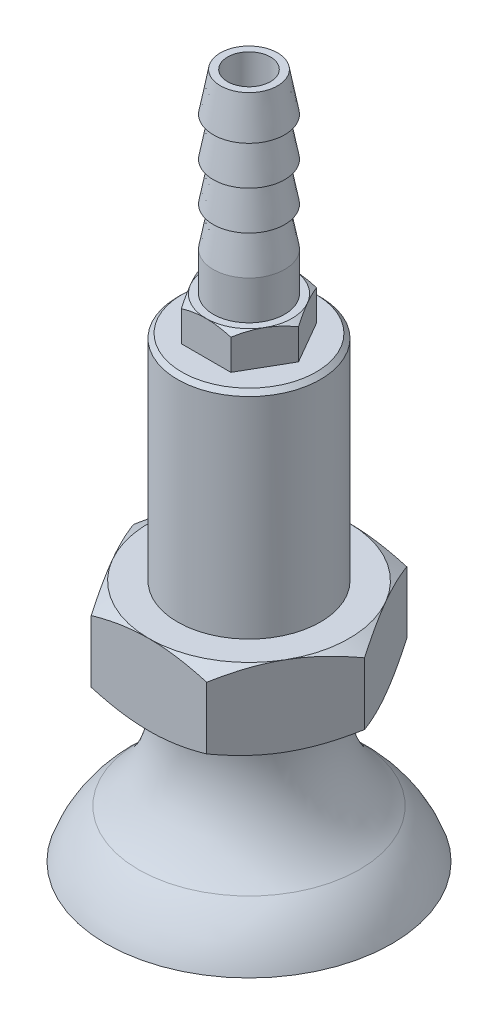
SolidWorks part; units mm, degrees
ref_plane "前视基准面" through (0, 0, 0) normal (0, 0, 1) x (1, 0, 0)
ref_plane "上视基准面" through (0, 0, 0) normal (0, 1, 0) x (1, 0, 0)
ref_plane "右视基准面" through (0, 0, 0) normal (1, 0, 0) x (0, 0, -1)
sketch "草图1" plane through (0, 0, 0) normal (0, 0, 1) x (1, 0, 0)
  line L0 (0, 24) -> (0, -24) construction
  line L1 (0, 24) -> (-2.5, 24)
  line L2 (-2.5, 24) -> (-2.5, 10.4)
  line L3 (-2.5, 10.4) -> (-3, 10.4)
  line L4 (-3, 10.4) -> (-3, 8)
  line L5 (-3, 8) -> (-5, 8)
  line L6 (-5, 8) -> (-5, 5.8)
  line L8 (-7, 5.8) -> (-7, -2.6)
  line L10 (-5, -2.6) -> (-5, -4.8)
  line L12 (-7, -7) -> (-7, -12.6)
  line L14 (-5, -12.6) -> (-5, -14)
  line L16 (-6, -19.5) -> (-10, -24)
  line L22 (0, -24) -> (-29.6075, -24) construction
  line L23 (-5, -4.8) -> (-5, -7)
  line L24 (-5, -14) -> (-6, -19.5)
  line L25 (-3.35, -20.4274) -> (-2.15, -20.4274)
  line L26 (-2.15, -20.4274) -> (-2.15, -9.8)
  line L27 (-2.15, -9.8) -> (0, -9.8)
  line L28 (-3.35, -20.4274) -> (-3.35, -21.7)
  arc A0 (-10, -24) -> (-6, -19.5) centre (-2.5797, -26.568) cw
  arc A1 (-6, -19.5) -> (-5, -14) centre (-15.9986, -14.8412) ccw
  arc A2 (-10, -24) -> (0, -21.4274) centre (0, -42.1495) cw
  point P3 (0, 0)
  point P21 (-7, 1.6)
  point P27 (-7, -9.8)
  point P31 (-2.5, -20.4274)
  dimension "D8" = 0.6
  dimension "D1" = 5
  dimension "B" = 48
  dimension "I" = 16
  dimension "D" = 22
  dimension "J" = 15
  dimension "D2" = 1.4
  dimension "S" = 14
  dimension "D3" = 4.5
  dimension "F" = 10
  dimension "D4" = 6
  dimension "D5" = 13.6
  dimension "D6" = 12
  dimension "D7" = 8.4
  dimension "Y" = 2.3
  dimension "Z" = 5
  dimension "E" = 14
  dimension "A" = 20
  dimension "D9" = 0.36
  dimension "D10" = 4.3
  dimension "D11" = 1.2
  dimension "D13" = 1
sketch "草图2" plane through (0, 0, 0) normal (0, 0, 1) x (1, 0, 0)
  line L0 (0, 24) -> (-2.5, 24) construction
  line L1 (-2.5, 24) -> (-2.5, 10.4) construction
  line L2 (-2.5, 10.4) -> (-3, 10.4) construction
  line L3 (-3, 10.4) -> (-3, 8) construction
  line L4 (-3, 8) -> (-5, 8) construction
  line L5 (-5, 8) -> (-5, 5.8) construction
  line L6 (-3.35, -20.4274) -> (-3.35, -21.7) construction
  line L7 (-3.35, -20.4274) -> (-2.15, -20.4274) construction
  line L8 (-2.15, -20.4274) -> (-2.15, -9.8) construction
  line L9 (-2.15, -9.8) -> (0, -9.8) construction
  line L10 (-3.35, -20.4274) -> (-3.35, -21.7)
  line L11 (-3.35, -20.4274) -> (-2.15, -20.4274)
  line L12 (-2.15, -20.4274) -> (-2.15, -9.8)
  line L13 (-2.15, -9.8) -> (0, -9.8)
  line L14 (-5, 10.4) -> (-5, 13.12) construction
  line L15 (-5, 21.28) -> (-5, 24) construction
  line L19 (0, 24) -> (-2, 24)
  line L20 (-2.5, 13.12) -> (-2.5, 10.4)
  line L21 (-2.5, 10.4) -> (-3, 10.4)
  line L22 (-3, 10.4) -> (-3, 8)
  line L23 (-3, 8) -> (-5, 8)
  line L24 (-5, 8) -> (-5, -14)
  line L25 (-5, 18.56) -> (-5, 21.28) construction
  line L26 (-5, 15.84) -> (-5, 18.56) construction
  line L27 (-5, 13.12) -> (-5, 15.84) construction
  line L38 (0, 24) -> (0, -9.8)
  line L39 (-2, 24) -> (-2.5, 21.28)
  line L40 (-2.5, 21.28) -> (-2, 21.28)
  line L41 (-2, 21.28) -> (-2.5, 18.56)
  line L42 (-2.5, 18.56) -> (-2, 18.56)
  line L43 (-2, 18.56) -> (-2.5, 15.84)
  line L44 (-2.5, 15.84) -> (-2, 15.84)
  line L45 (-2, 15.84) -> (-2.5, 13.12)
  arc A0 (-6, -19.5) -> (-10, -24) centre (-2.5797, -26.568) ccw construction
  arc A1 (-6, -19.5) -> (-5, -14) centre (-15.9986, -14.8412) ccw construction
  arc A2 (-6, -19.5) -> (-10, -24) centre (-2.5797, -26.568) ccw
  arc A3 (-6, -19.5) -> (-5, -14) centre (-15.9986, -14.8412) ccw
  arc A4 (0, -21.4274) -> (-10, -24) centre (0, -42.1495) ccw construction
  arc A5 (-3.35, -21.7) -> (-10, -24) centre (0, -42.1495) ccw
  dimension "D4" = 0.5
revolve "旋转1" add sketch "草图2" angle 360 about L0
cosmetic thread "装饰螺纹线1" parameters "D1"=22, "D2"=8.6
cosmetic thread "装饰螺纹线2" parameters "D2"=5
sketch "草图4" plane through (0, 0, 0) normal (0, 1, 0) x (1, 0, 0)
  line L1 (3.4641, 0) -> (1.7321, 3)
  line L2 (1.7321, 3) -> (-1.7321, 3)
  line L3 (-1.7321, 3) -> (-3.4641, 0)
  line L4 (-3.4641, 0) -> (-1.7321, -3)
  line L5 (-1.7321, -3) -> (1.7321, -3)
  line L6 (1.7321, -3) -> (3.4641, 0)
  circle A1 centre (0, 0) radius 3 construction
  circle A2 centre (0, 0) radius 3 construction
  circle A3 centre (0, 0) radius 3 construction
  dimension "D1" = 3
extrude "凸台-拉伸1" add sketch "草图4" against normal up to vertex (-8 mm away) from vertex up to point (-3, 8, 0) starting at point (-3, 10.4, 0)
chamfer "倒角1" distance 0.3 angle 45 1 edges at (-5, 8, 0)
sketch "草图5" plane through (0, 0, 0) normal (0, 1, 0) x (1, 0, 0)
  line L1 (8.0829, 0) -> (4.0415, 7)
  line L2 (4.0415, 7) -> (-4.0415, 7)
  line L3 (-4.0415, 7) -> (-8.0829, 0)
  line L4 (-8.0829, 0) -> (-4.0415, -7)
  line L5 (-4.0415, -7) -> (4.0415, -7)
  line L6 (4.0415, -7) -> (8.0829, 0)
  circle A1 centre (0, 0) radius 7 construction
  circle A2 centre (0, 0) radius 7 construction
extrude "凸台-拉伸3" add sketch "草图5" against normal up to vertex (12.6 mm away) from vertex up to point (-7, -12.6, 0) starting at point (-7, -7, 0)
sketch "草图6" plane through (0, 0, 0) normal (0, 1, 0) x (1, 0, 0)
  circle A0 centre (0, 0) radius 3 construction
  circle A1 centre (0, 0) radius 3
extrude "切除-拉伸1" cut sketch "草图6" against normal up to vertex (-8 mm away) draft 60 from vertex flip side to cut up to point (-3, 8, 0) starting at point (-3, 10.4, 0)
sketch "草图7" plane through (0, 0, 0) normal (0, 1, 0) x (1, 0, 0)
  circle A0 centre (0, 0) radius 7 construction
  circle A1 centre (0, 0) radius 7
extrude "切除-拉伸6" cut sketch "草图7<5>" against normal up to vertex (12.6 mm away) draft 60 from vertex flip side to cut up to point (-7, -12.6, 0) starting at point (-7, -7, 0)
sketch "草图7<5>" plane through (0, 0, 0) normal (0, 1, 0) x (1, 0, 0) same geometry as "草图7"
extrude "切除-拉伸7" cut sketch "草图7" along normal up to vertex (-7 mm away) draft 60 from vertex flip side to cut up to point (-7, -7, 0) starting at point (-7, -12.6, 0)
sketch "草图8" plane through (0, 0, 0) normal (0, 1, 0) x (1, 0, 0)
  circle A0 centre (0, 0) radius 1.5
  dimension "D1" = 3
extrude "切除-拉伸8" cut sketch "草图8" along normal through all from vertex starting at point (-3, 8, 0)
fillet "圆角1" radius 8 1 edges at (-6, -19.5, 0)
